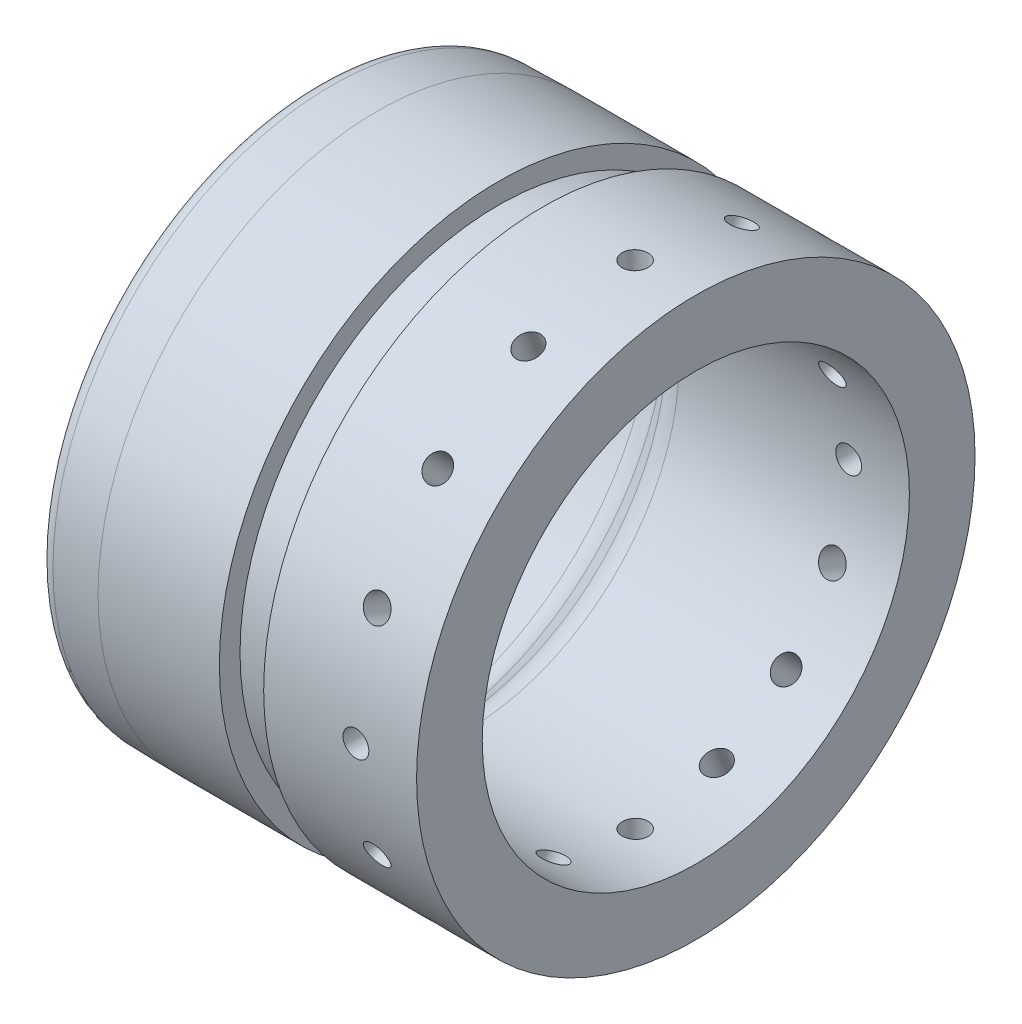
SolidWorks part; units mm, degrees
material "6061-T6 (SS)"
ref_plane "Front Plane" through (0, 0, 0) normal (0, 0, 1) x (1, 0, 0)
ref_plane "Top Plane" through (0, 0, 0) normal (0, 1, 0) x (1, 0, 0)
ref_plane "Right Plane" through (0, 0, 0) normal (1, 0, 0) x (0, 0, -1)
sketch "Sketch1" plane through (0, 0, 0) normal (0, 0, 1) x (1, 0, 0)
  line L12 (0.0186, 58.9466) -> (98.3939, 58.9466) construction
  line L19 (-3.9714, 6.5774) -> (1.8338, 12.3827)
  line L28 (6.324, 14.2426) -> (54.4937, 14.2426)
  line L29 (54.4937, 0.5012) -> (54.4937, 14.2426)
  line L30 (13.2187, 0.5012) -> (13.2187, 4.8192)
  line L31 (13.2187, 4.8192) -> (22.4897, 4.8192)
  line L32 (22.4897, 4.8192) -> (22.4897, 0.5012)
  line L33 (22.4897, 0.5012) -> (54.4937, 0.5012)
  line L34 (-24.8999, 0.5012) -> (13.2187, 0.5012)
  line L35 (-24.8999, 0.5012) -> (-12.1813, 0.5012)
  line L36 (-12.1813, 0.5012) -> (-24.8999, 0.7232)
  line L38 (-24.8999, 4.7176) -> (-8.4616, 4.7176)
  line L39 (-24.8999, 4.7176) -> (-24.8999, 0.7232)
  line L40 (-24.8999, 0.7232) -> (-24.8999, 0.5012)
  arc A0 (-3.9714, 6.5774) -> (-8.4616, 4.7176) centre (-8.4616, 11.0676) cw
  arc A1 (6.324, 14.2426) -> (1.8338, 12.3827) centre (6.324, 7.8926) ccw
  point P8 (-5.8499, 4.2164)
  point P22 (3.6751, 13.7414)
  dimension "D15" = 4.7176
  dimension "D16" = 4.8192
  dimension "D8" = 3.9714
  dimension "D9" = 5.8499
  dimension "D1" = 6.35
  dimension "D3" = 3.6751
  dimension "D2" = 1.8338
  dimension "D4" = 6.324
  dimension "D5" = 13.2187
  dimension "D6" = 22.4897
  dimension "D7" = 54.4937
  dimension "D10" = 0.5012
  dimension "D11" = 12.1813
  dimension "D12" = 24.8999
  dimension "D13" = 0.7232
  dimension "D14" = 4.2164
  dimension "D21" = 13.7414
  dimension "D23" = 58.9466
revolve "Revolve1" add sketch "Sketch1" angle 360 about L12 region at (22.3214, 6.9343, 0)
ref_plane "Tap Reference Plane" through (0, 0, -58.4454) normal (0, 0, -1) x (-1, 0, 0)
sketch "Tap Reference" plane through (0, 0, -58.4454) normal (0, 0, -1) x (-1, 0, 0)
  line L0 (-54.4937, 58.9466) -> (-41.7937, 58.9466)
  line L2 (-54.4937, 117.392) -> (-54.4937, 0.5012) construction
  point P5 (-41.7937, 58.9466)
hole_wizard "Tap Drill for 1/4-28 Tap1" positions "Sketch4" profile "Sketch6" hole size "1/4-28" standard "ANSI Inch" end condition through all
sketch "Sketch4" plane through (0, 0, -58.4454) normal (0, 0, -1) x (-1, 0, 0)
  point P0 (-41.7937, 58.9466)
sketch "Sketch6" plane through (41.7937, 58.9466, -58.4454) normal (1, 0, 0) x (0, 1, 0)
  line L0 (0, 0) -> (0, 116.8908)
  line L1 (0, 116.8908) -> (2.7051, 116.8908)
  line L2 (2.7051, 116.8908) -> (2.7051, 0)
  line L5 (2.7051, 0) -> (0, 0)
  line L11 (0, -6.35) -> (0, 107.95) construction
  dimension "Thru Hole Dia." = 5.4102
  dimension "Thru Hole Depth" = 116.8908
pattern_circular "Tap Pattern" count 16 over 360 about axis through (0.0186, 58.9466, 0) along (1, 0, 0) of "Tap Drill for 1/4-28 Tap1" reverse direction yes
fillet "Fillet1" radius 3.175 1 edges at (-24.8999, 58.9466, 58.2234)
